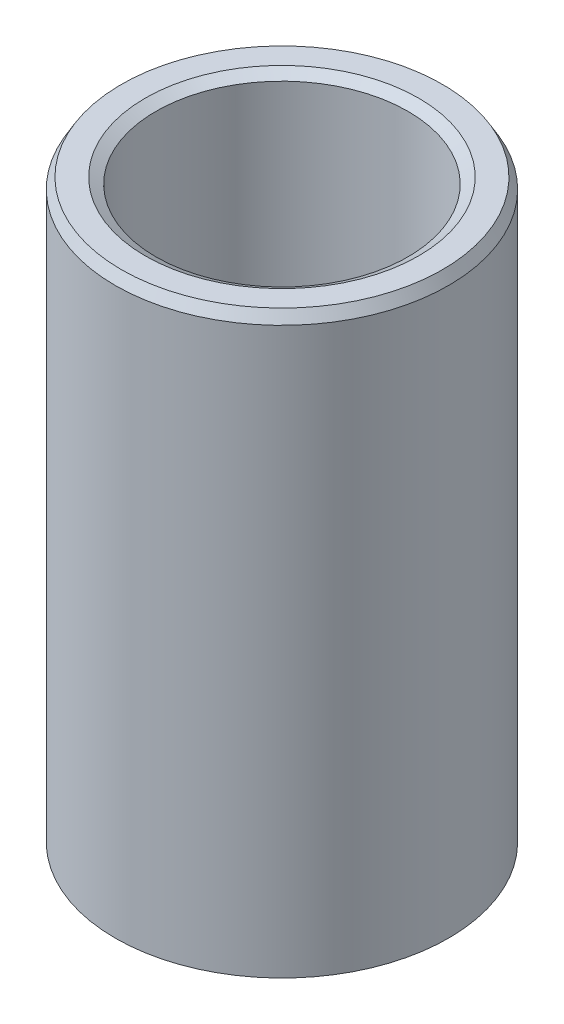
SolidWorks part; units mm, degrees
ref_plane "Front Plane" through (0, 0, 0) normal (0, 0, 1) x (1, 0, 0)
ref_plane "Top Plane" through (0, 0, 0) normal (0, 1, 0) x (1, 0, 0)
ref_plane "Right Plane" through (0, 0, 0) normal (1, 0, 0) x (0, 0, -1)
sketch "Sketch1" plane through (0, 0, 0) normal (0, 1, 0) x (1, 0, 0)
  circle A0 centre (0, 0) radius 60
  dimension "SLEEVE_OD" = 120
extrude "Boss-Extrude1" add sketch "Sketch1" along normal blind 209.5222
sketch "Sketch2" plane through (0, 0, 0) normal (0, 1, 0) x (1, 0, 0)
  circle A0 centre (0, 0) radius 45.385
  dimension "BORE_D" = 90.7701
extrude "Cut-Extrude1" cut sketch "Sketch2" along normal through all
chamfer "Chamfer1" distance 3.824 angle 30 4 edges at (0, 209.5222, 45.385) (0, 0, 45.385) (0, 0, 60) (0, 209.5222, 60) first distance on face at (0, 209.5222, 45.385) first distance on face at (0, 0, 45.385) first distance on face at (0, 209.5222, 60)
